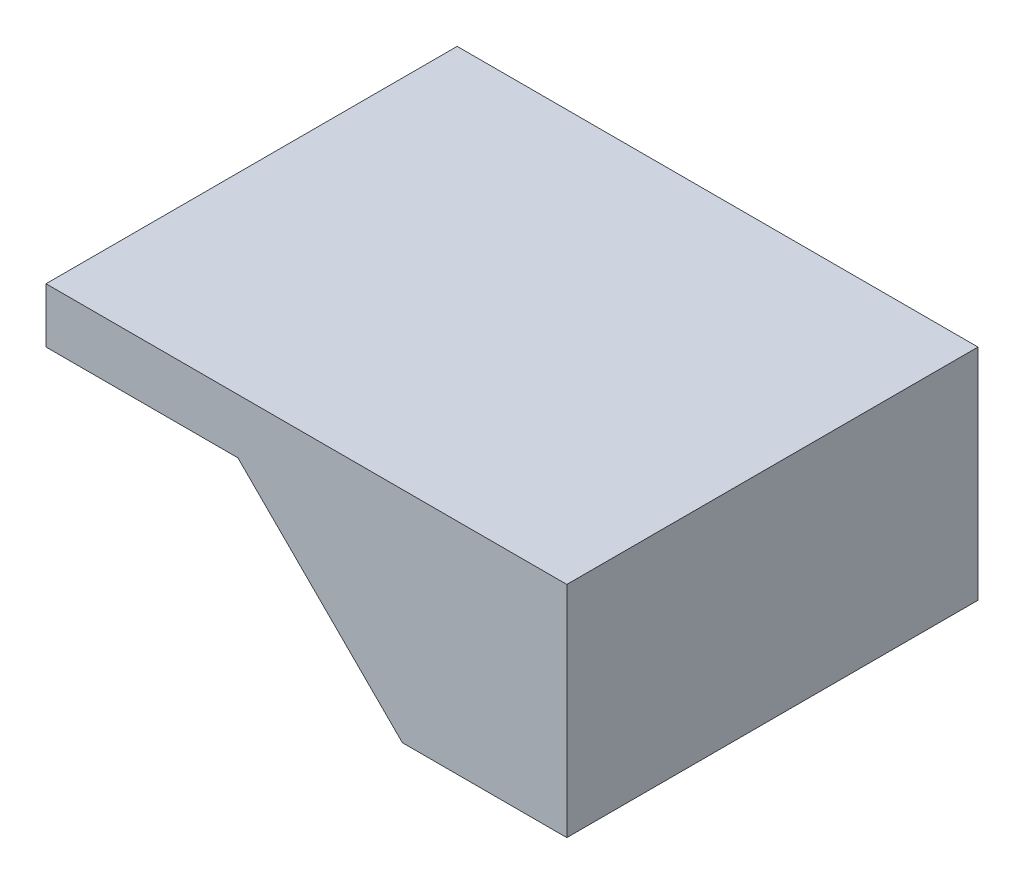
SolidWorks part; units mm, degrees
ref_plane "前视基准面" through (0, 0, 0) normal (0, 0, 1) x (1, 0, 0)
ref_plane "上视基准面" through (0, 0, 0) normal (0, 1, 0) x (1, 0, 0)
ref_plane "右视基准面" through (0, 0, 0) normal (1, 0, 0) x (0, 0, -1)
sketch "草图1" plane through (0, 0, 0) normal (0, 0, 1) x (1, 0, 0)
  line L0 (0, 0) -> (70, 0)
  line L1 (70, 0) -> (120, -50)
  line L2 (120, -50) -> (210, -50)
  line L3 (210, -50) -> (210, 20)
  line L4 (210, 20) -> (0, 20)
  line L5 (0, 20) -> (0, 0)
  dimension "D1" = 50
  dimension "D2" = 45
  dimension "D3" = 120
  dimension "D4" = 210
  dimension "D5" = 70
extrude "凸台-拉伸1" add sketch "草图1" along normal mid plane 150
ref_plane "基准面1" through (35, 35, 0) normal (-0.7071, -0.7071, 0) x (-0.7071, 0.7071, 0)
ref_plane "基准面2" through (85, -85, 0) normal (-0.7071, 0.7071, 0) x (0, 0, -1)
sketch "草图2" plane through (85, -85, 0) normal (-0.7071, 0.7071, 0) x (0, 0, -1)
  line L0 (0, -113.1371) -> (0, 39.1732) construction
  line L1 (-75, -113.1371) -> (75, -113.1371) construction
  line L2 (75, -49.4975) -> (-98.1322, -49.4975) construction
  line L3 (38.5, -49.4975) -> (-38.5, -49.4975) construction
  line L4 (75, -49.4975) -> (75, -113.1371) construction
  line L5 (5, -44.4975) -> (10, -41.9975)
  line L7 (5, -44.4975) -> (5, -54.4975)
  line L8 (5, -54.4975) -> (-5, -54.4975)
  line L9 (-5, -44.4975) -> (-5, -54.4975)
  line L10 (5, -44.4975) -> (-5, -54.4975) construction
  line L11 (5, -54.4975) -> (-5, -44.4975) construction
  line L12 (10, -41.9975) -> (10, -39.4975)
  line L13 (10, -39.4975) -> (-10, -39.4975)
  line L14 (-10, -39.4975) -> (-10, -41.9975)
  line L15 (-10, -41.9975) -> (-5, -44.4975)
  point P11 (0, -49.4975)
  dimension "D1" = 10
  dimension "D3" = 10
  dimension "D4" = 10
  dimension "D5" = 2.5
  dimension "D6" = 2.5
extrude "凸台-拉伸2" add sketch "草图2" along normal up to surface (78.2107 mm away) up to face at (35, 0, 0)
sketch "草图3" plane through (0, 0, 75) normal (0, 0, 1) x (1, 0, 0)
  line L0 (210, -50) -> (61.973, -50)
  line L1 (61.973, -50) -> (60.4893, -78.8369)
  line L2 (60.4893, -78.8369) -> (236.8364, -81.3804)
  line L3 (236.8364, -81.3804) -> (210, -50)
sketch "草图4" plane through (0, 0, 75) normal (0, 0, 1) x (1, 0, 0)
  line L0 (120, -50) -> (130, -60)
  line L1 (130, -60) -> (210, -60)
  line L2 (210, -60) -> (210, -50)
  line L3 (120, -50) -> (210, -50) construction
  line L4 (120, -50) -> (210, -50)
  dimension "D1" = 10
  dimension "D2" = 45
extrude "凸台-拉伸3" add sketch "草图4" against normal up to surface (150 mm away) up to face at (101.6667, -10, -75)
ref_plane "基准面3" through (95, -95, 0) normal (0.7071, -0.7071, 0) x (0, 0, 1)
extrude "凸台-拉伸4" add sketch "草图2<2>" against normal up to surface (14.1421 mm away) up to plane "基准面3"
sketch "草图2<2>" plane through (85, -85, 0) normal (-0.7071, 0.7071, 0) x (0, 0, -1) same geometry as "草图2"
sketch "草图5" plane through (0, 0, -75) normal (0, 0, -1) x (-1, 0, 0)
  line L0 (-210, -60) -> (-130, -60) construction
  line L1 (-187.5706, -60) -> (-77.3284, -60)
  line L2 (-187.5706, -60) -> (-187.5706, -96.039)
  line L3 (-187.5706, -96.039) -> (-77.3284, -96.039)
  line L4 (-77.3284, -60) -> (-77.3284, -96.039)
extrude "切除-拉伸2" cut sketch "草图5" against normal through all both and the other way through all
sketch "草图6" plane through (0, 0, 75) normal (0, 0, 1) x (1, 0, 0)
  line L0 (190, -60) -> (190, -230) construction
  line L1 (190, -122.1244) -> (230.5656, -122.1244)
  line L2 (190, -122.1244) -> (190, 38.7452)
  line L3 (190, 38.7452) -> (230.5656, 38.7452)
  line L4 (230.5656, -122.1244) -> (230.5656, 38.7452)
extrude "切除-拉伸3" cut sketch "草图6" against normal through all both and the other way through all
